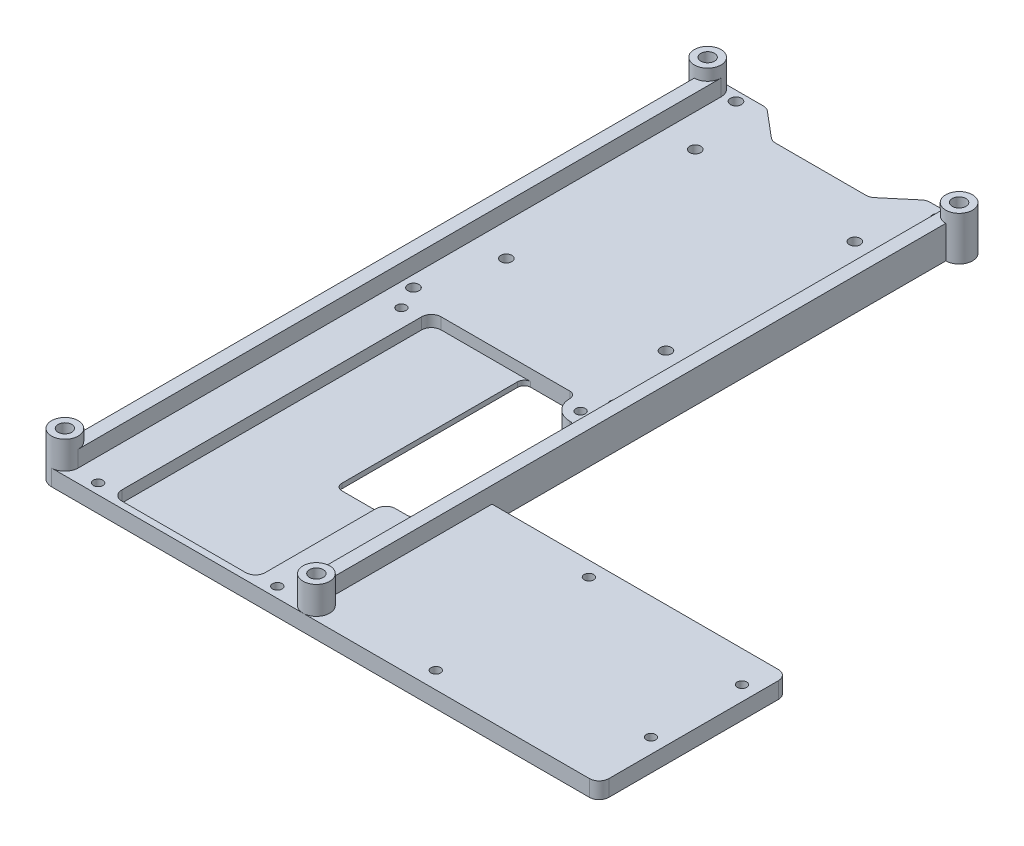
SolidWorks part; units mm, degrees
ref_plane "Plan de face" through (0, 0, 0) normal (0, 0, 1) x (1, 0, 0)
ref_plane "Plan de dessus" through (0, 0, 0) normal (0, 1, 0) x (1, 0, 0)
ref_plane "Plan de droite" through (0, 0, 0) normal (1, 0, 0) x (0, 0, -1)
sketch "Esquisse1" plane through (0, 0, 0) normal (0, 1, 0) x (1, 0, 0)
  line L0 (0, 0) -> (0, 29016.7345) construction
  line L1 (0, 0) -> (29016.7345, 0) construction
  line L2 (-15, 45) -> (15, 45)
  line L3 (15, 45) -> (24.5, 53)
  line L4 (24.5, 53) -> (34.5, 53)
  line L5 (34.5, 53) -> (34.5, -53)
  line L8 (34.5, -152.5) -> (-34.5, -152.5)
  line L9 (34.5, -53) -> (-34.5, -53) construction
  line L10 (34.5, -53) -> (-34.5, -53) construction
  line L11 (-24.5, 31) -> (-24.5, -27) construction
  line L14 (-34.5, 53) -> (-34.5, -53)
  line L15 (-24.5, 53) -> (-34.5, 53)
  line L16 (-15, 45) -> (-24.5, 53)
  line L17 (-27.5, -149.3) -> (27.5, -149.3) construction
  line L18 (-27.5, -56.2) -> (27.5, -56.2) construction
  line L19 (-24.5, 31) -> (24.5, 31) construction
  line L20 (-31, 50) -> (-31, -49) construction
  line L21 (-31, -49) -> (31, -49) construction
  line L22 (34.5, -53) -> (34.5, -94.5)
  line L23 (-31, 50) -> (31, 50) construction
  line L24 (34.5, -152.5) -> (129.5, -152.5)
  line L26 (34.5, -94.5) -> (129.5, -94.5)
  line L27 (129.5, -152.5) -> (129.5, -94.5)
  line L29 (124.96, -104.12) -> (124.96, -132.06) construction
  line L30 (72.89, -99.04) -> (124.96, -104.12) construction
  line L31 (72.89, -99.04) -> (74.16, -147.3) construction
  line L32 (74.16, -147.3) -> (124.96, -132.06) construction
  line L33 (-24.5, -27) -> (24.5, -27) construction
  line L34 (24.5, -27) -> (24.5, 31) construction
  line L35 (31, 50) -> (31, -49) construction
  line L36 (-27.5, -56.2) -> (-27.5, -149.3) construction
  line L37 (27.5, -149.3) -> (27.5, -56.2) construction
  line L38 (34.5, -94.5) -> (34.5, -152.5) construction
  line L39 (-34.5, -53) -> (-34.5, -152.5)
  circle A0 centre (31, 50) radius 1.7
  circle A1 centre (31, -49) radius 1.7
  circle A2 centre (27.5, -56.2) radius 1.45
  circle A3 centre (27.5, -149.3) radius 1.45
  circle A4 centre (-27.5, -149.3) radius 1.45
  circle A5 centre (-27.5, -56.2) radius 1.45
  circle A6 centre (-31, -49) radius 1.7
  circle A7 centre (-31, 50) radius 1.7
  circle A8 centre (-24.5, 31) radius 1.7
  circle A9 centre (24.5, 31) radius 1.7
  circle A10 centre (72.89, -99.04) radius 1.45
  circle A12 centre (24.5, -27) radius 1.7
  circle A13 centre (-24.5, -27) radius 1.7
  circle A14 centre (124.96, -104.12) radius 1.45
  circle A18 centre (124.96, -132.06) radius 1.45
  circle A19 centre (74.16, -147.3) radius 1.45
  point P5 (0, -49)
  point P14 (34.5, 0)
  point P28 (0, -115)
  point P29 (0, -53)
  point P30 (0, -53)
  point P39 (0, -152.5)
  point P42 (0, 45)
  point P76 (0, -149.3)
  point P78 (0, -56.2)
  dimension "D1" = 3.4
  dimension "D29" = 2.9
  dimension "D12" = 2.9
  dimension "D2" = 3
  dimension "D4" = 15
  dimension "D6" = 10
  dimension "D8" = 106
  dimension "D18" = 58
  dimension "D19" = 19
  dimension "D7" = 8
  dimension "D24" = 58
  dimension "D25" = 95
  dimension "D27" = 4.54
  dimension "D28" = 9.62
  dimension "D30" = 95.572
  dimension "D31" = 106.699
  dimension "D32" = 74.808
  dimension "D33" = 48.26
  dimension "D34" = 53.0368
  dimension "D13" = 49
  dimension "D17" = 99
  dimension "D11" = 55
  dimension "D14" = 93.1
  dimension "D9" = 41.5
  dimension "D10" = 3.2
  dimension "D15" = 3.2
  dimension "D16" = 62
  dimension "D20" = 1.8
  dimension "D5" = 69
extrude "Boss.-Extru.1" add sketch "Esquisse1" along normal blind 5
ref_plane "Plan1 millieu" through (0, 0, 49.75) normal (0, 0, 1) x (1, 0, 0)
sketch "Esquisse2" plane through (0, 5, 0) normal (0, 1, 0) x (1, 0, 0)
  line L0 (34.5, -94.5) -> (34.5, -152.5) construction
  line L1 (-22, -150.5) -> (22, -150.5)
  line L2 (-22, -150.5) -> (-22, -52.5)
  line L3 (-22, -52.5) -> (22, -52.5)
  line L4 (22, -150.5) -> (22, -52.5)
  line L5 (-34.5, -152.5) -> (129.5, -152.5) construction
  line L8 (34.5, -87.5) -> (-34.5, -87.5) construction
  line L9 (34.5, -94.5) -> (34.5, 53) construction
  line L10 (-34.5, 53) -> (-34.5, -152.5) construction
  line L11 (0, -52.5) -> (0, -150.5) construction
  point P17 (0, -87.5)
  dimension "D1" = 44
  dimension "D2" = 2
  dimension "D3" = 65
  dimension "D5" = 98
extrude "Enlèv. mat.-pcb ecran ino" cut sketch "Esquisse2" against normal blind 3.5
sketch "Esquisse3" plane through (0, 5, 0) normal (0, 1, 0) x (1, 0, 0)
  line L0 (30.5, -110.5) -> (30.5, -60.5)
  line L1 (6.5, -110.5) -> (30.5, -110.5)
  line L2 (6.5, -110.5) -> (6.5, -52.5)
  line L5 (30.5, -60.5) -> (22.5, -60.5)
  line L6 (22.5, -60.5) -> (22.5, -52.5)
  line L7 (22.5, -52.5) -> (6.5, -52.5)
  line L8 (22, -52.5) -> (-22, -52.5) construction
  line L9 (34.5, -94.5) -> (34.5, 53) construction
  circle A1 centre (27.5, -56.2) radius 1.45 construction
  dimension "D3" = 5
  dimension "D1" = 4
  dimension "D2" = 8
  dimension "D4" = 16
  dimension "D6" = 50
extrude "Enlèv. mat.- pcb excroissance ecran ino" cut sketch "Esquisse3" against normal through all
fillet "Congé excroissance pcb ecran ino" radius 2 5 edges at (30.5, 2.5, 110.5) (6.5, 0.75, 110.5) (6.5, 0.75, 52.5) (30.5, 2.5, 60.5) (22.5, 2.5, 52.5)
sketch "Esquisse10" plane through (0, 0, 0) normal (0, -1, 0) x (1, 0, 0)
  line L1 (-34.5, -53) -> (-38.6, -53)
  line L2 (-34.5, -53) -> (-34.5, -44.8)
  line L3 (-34.5, -44.8) -> (-38.6, -44.8)
  line L15 (0, -7.425) -> (0, 7.425) construction
  line L17 (34.5, -44.8) -> (38.6, -44.8)
  line L18 (34.5, -53) -> (34.5, -44.8)
  line L19 (34.5, -53) -> (38.6, -53)
  line L20 (11.9793, 49.75) -> (-11.9793, 49.75) construction
  line L21 (34.5, 152.5) -> (38.6, 152.5)
  line L22 (34.5, 152.5) -> (34.5, 144.3)
  line L23 (34.5, 144.3) -> (38.6, 144.3)
  line L24 (-34.5, 144.3) -> (-38.6, 144.3)
  line L25 (-34.5, 152.5) -> (-34.5, 144.3)
  line L26 (-34.5, 152.5) -> (-38.6, 152.5)
  arc A0 (-38.6, -53) -> (-38.6, -44.8) centre (-38.6, -48.9) cw
  circle A1 centre (-38.6, -48.9) radius 2.1
  circle A8 centre (38.6, -48.9) radius 2.1
  arc A9 (38.6, -53) -> (38.6, -44.8) centre (38.6, -48.9) ccw
  arc A10 (38.6, 152.5) -> (38.6, 144.3) centre (38.6, 148.4) cw
  circle A11 centre (38.6, 148.4) radius 2.1
  circle A12 centre (-38.6, 148.4) radius 2.1
  arc A13 (-38.6, 152.5) -> (-38.6, 144.3) centre (-38.6, 148.4) ccw
  dimension "D1" = 4.2
  dimension "D2" = 2
  dimension "D3" = 2
extrude "Boss.-Extru.3" add sketch "Esquisse10" against normal blind 13.5
sketch "Esquisse13" plane through (0, 13.5, 0) normal (0, 1, 0) x (1, 0, 0)
  line L0 (0, -7.425) -> (0, 7.425) construction
  line L1 (-11.9793, -49.75) -> (11.9793, -49.75) construction
  circle A0 centre (-38.6, -148.4) radius 4.1
  arc A1 (-38.6, -144.3) -> (-38.6, -152.5) centre (-38.6, -148.4) ccw construction
  circle A2 centre (-38.6, -148.4) radius 5.7983
  circle A3 centre (38.6, -148.4) radius 4.1
  circle A4 centre (38.6, -148.4) radius 5.7983
  circle A5 centre (38.6, 48.9) radius 5.7983
  circle A6 centre (38.6, 48.9) radius 4.1
  circle A7 centre (-38.6, 48.9) radius 5.7983
  circle A8 centre (-38.6, 48.9) radius 4.1
extrude "Enlèv. mat.-Extru.4" cut sketch "Esquisse13" against normal up to surface (8.5 mm away) up to face at (22.0471, 5, 49.4294)
sketch "Esquisse14" plane through (0, 5, 0) normal (0, 1, 0) x (1, 0, 0)
  circle A0 centre (38.6, -148.4) radius 2.1
  circle A1 centre (38.6, -148.4) radius 2.1 construction
extrude "Enlèv. mat.-Extru.5" cut sketch "Esquisse14" against normal through all
fillet "Congé1" radius 6 1 edges at (22.5, 2.5, 60.5)
sketch "Esquisse19" plane through (0, 0, 0) normal (0, 1, 0) x (1, 0, 0)
  line L2 (-34.5, 48.9) -> (-34.5, -148.4)
  line L5 (-38.6, 44.8) -> (-38.6, -144.3)
  line L6 (0, -7.425) -> (0, 7.425) construction
  line L7 (38.6, 44.8) -> (38.6, -144.3)
  line L8 (34.5, 48.9) -> (34.5, -148.4)
  arc A2 (-38.6, 44.8) -> (-38.6, 53) centre (-38.6, 48.9) ccw construction
  arc A3 (-34.5, 48.9) -> (-38.6, 44.8) centre (-38.6, 48.9) cw
  arc A4 (-38.6, -152.5) -> (-38.6, -144.3) centre (-38.6, -148.4) ccw construction
  arc A5 (-34.5, -148.4) -> (-38.6, -144.3) centre (-38.6, -148.4) ccw
  arc A6 (34.5, -148.4) -> (38.6, -144.3) centre (38.6, -148.4) cw
  arc A7 (34.5, 48.9) -> (38.6, 44.8) centre (38.6, 48.9) ccw
extrude "Boss.-Extru.10" add sketch "Esquisse19" along normal blind 10 separate body
fillet "Congé global" radius 3 11 edges at (-22, 3.25, 150.5) (22, 3.25, 150.5) (22, 3.25, 110.5) (-22, 3.25, 52.5) (15, 2.5, -45) (24.5, 2.5, -53) (-15, 2.5, -45) (-24.5, 2.5, -53) (129.5, 2.5, 152.5) (129.5, 2.5, 94.5) (34.5, 2.5, 94.5)
equation "\"D3@Esquisse10\"=\"D2@Esquisse10\""
equation "\"D10@Esquisse1\"=(\"D9@Esquisse1\"+\"D24@Esquisse1\" - \"D14@Esquisse1\") / 2"
